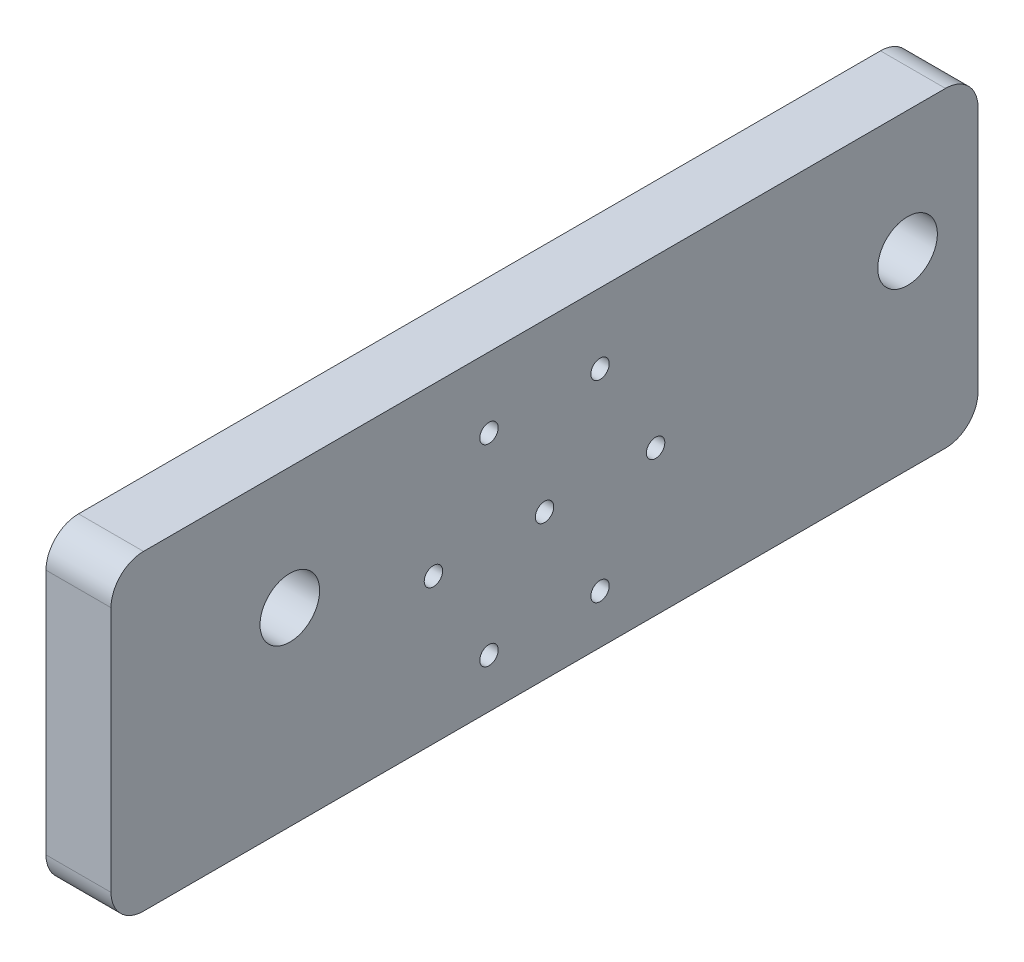
SolidWorks part; units mm, degrees
ref_plane "Front Plane" through (0, 0, 0) normal (0, 0, 1) x (1, 0, 0)
ref_plane "Top Plane" through (0, 0, 0) normal (0, 1, 0) x (1, 0, 0)
ref_plane "Right Plane" through (0, 0, 0) normal (1, 0, 0) x (0, 0, -1)
sketch "Sketch1" plane through (0, 0, 0) normal (1, 0, 0) x (0, 0, -1)
  line L0 (-10.25, -0.975) -> (10.25, -0.975) construction
  line L1 (-40, 14.375) -> (40, 14.375)
  line L2 (-40, 14.375) -> (-40, -14.375)
  line L3 (-40, -14.375) -> (40, -14.375)
  line L4 (40, 14.375) -> (40, -14.375)
  line L5 (-40, 14.375) -> (40, -14.375) construction
  line L6 (-40, -14.375) -> (40, 14.375) construction
  line L7 (5.125, -9.8518) -> (-5.125, 7.9018) construction
  line L8 (5.125, 7.9018) -> (-5.125, -9.8518) construction
  point P0 (0, 0)
  point P6 (-23.5, 3.125)
  point P7 (33.5, 3.125)
  point P8 (-10.25, -0.975)
  point P9 (10.25, -0.975)
  point P12 (0, -0.975)
  dimension "D1" = 28.75
  dimension "D2" = 80
  dimension "D3" = 11.25
  dimension "D4" = 16.5
  dimension "D5" = 6.5
  dimension "D6" = 13.4
  dimension "D7" = 20.5
  dimension "D8" = 60
  dimension "D9" = 60
extrude "Boss-Extrude1" add sketch "Sketch1" along normal blind 6
hole_wizard "M5 Clearance Hole1" positions "Sketch3" profile "Sketch2" hole size "M5" standard "ANSI Metric" end condition through all
sketch "Sketch3" plane through (0, 0, 0) normal (-1, 0, 0) x (0, 0, 1)
  point P0 (-33.5, 3.125)
  point P3 (23.5, 3.125)
sketch "Sketch2" plane through (0, 3.125, -33.5) normal (0, 1, 0) x (0, 0, 1)
  line L0 (0, 0) -> (0, 6)
  line L1 (0, 6) -> (2.75, 6)
  line L2 (2.75, 6) -> (2.75, 0)
  line L5 (2.75, 0) -> (0, 0)
  line L11 (0, -6.35) -> (0, 107.95) construction
  dimension "Thru Hole Dia." = 5.5
  dimension "Thru Hole Depth" = 6
hole_wizard "M1.6 Clearance Hole1" positions "Sketch8" profile "Sketch7" hole size "M1.6" standard "ANSI Metric" end condition through all
sketch "Sketch8" plane through (0, 0, 0) normal (-1, 0, 0) x (0, 0, 1)
  point P0 (-10.25, -0.975)
  point P3 (10.25, -0.975)
  point P7 (0, -0.975)
  point P10 (-5.125, -9.8518)
  point P12 (5.125, -9.8518)
  point P14 (5.125, 7.9018)
  point P16 (-5.125, 7.9018)
sketch "Sketch7" plane through (0, -0.975, -10.25) normal (0, 1, 0) x (0, 0, 1)
  line L0 (0, 0) -> (0, 6)
  line L1 (0, 6) -> (0.85, 6)
  line L2 (0.85, 6) -> (0.85, 0)
  line L5 (0.85, 0) -> (0, 0)
  line L11 (0, -6.35) -> (0, 107.95) construction
  dimension "Thru Hole Dia." = 1.7
  dimension "Thru Hole Depth" = 6
sketch "Sketch9" plane through (6, 0, 0) normal (1, 0, 0) x (0, 0, -1)
  line L0 (-10.25, -0.975) -> (10.25, -0.975) construction
  line L1 (-14.75, -12.8518) -> (14.75, -12.8518)
  line L2 (-14.75, -12.8518) -> (-14.75, 10.9018)
  line L3 (-14.75, 10.9018) -> (14.75, 10.9018)
  line L4 (14.75, -12.8518) -> (14.75, 10.9018)
  line L5 (-14.75, -12.8518) -> (14.75, 10.9018) construction
  line L6 (-14.75, 10.9018) -> (14.75, -12.8518) construction
  point P0 (0, -0.975)
  dimension "D1" = 3
  dimension "D2" = 4.5
extrude "Cut-Extrude1" cut sketch "Sketch9" along normal blind 2 from surface starting at face at (0, -0.975, -9.4)
fillet "Fillet1" radius 2 4 edges at (1, 10.9018, -14.75) (1, -12.8518, -14.75) (1, -12.8518, 14.75) (1, 10.9018, 14.75)
fillet "Fillet2" radius 3 4 edges at (3, -14.375, -40) (3, 14.375, -40) (3, 14.375, 40) (3, -14.375, 40)
